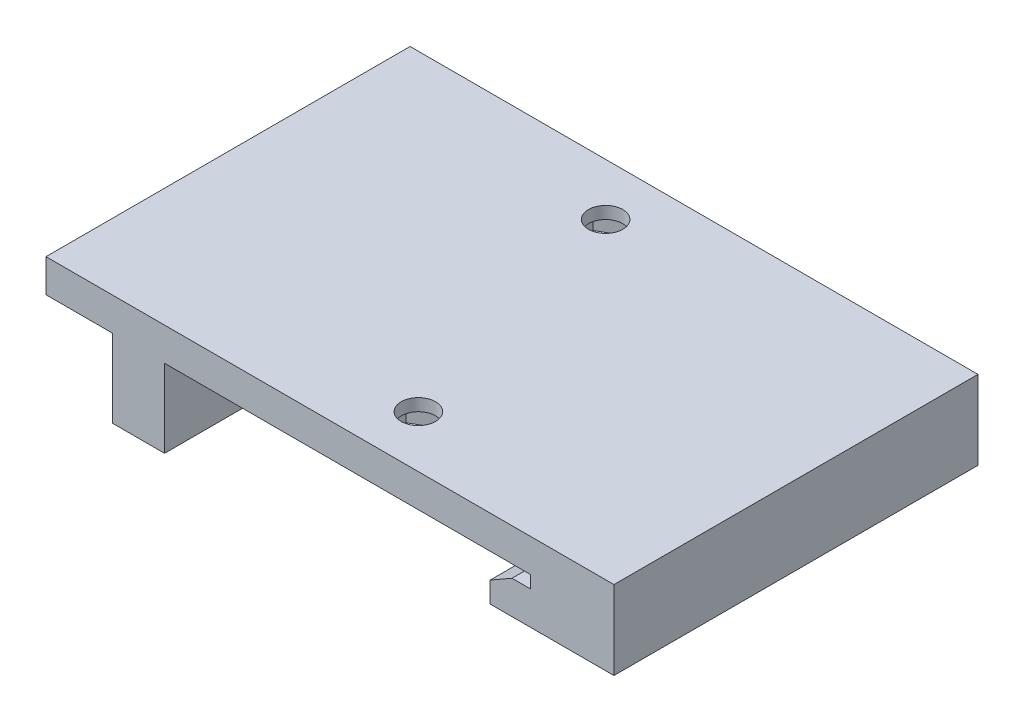
SolidWorks part; units mm, degrees
ref_plane "Front Plane" through (0, 0, 0) normal (0, 0, 1) x (1, 0, 0)
ref_plane "Top Plane" through (0, 0, 0) normal (0, 1, 0) x (1, 0, 0)
ref_plane "Right Plane" through (0, 0, 0) normal (1, 0, 0) x (0, 0, -1)
sketch "Sketch1" plane through (0, 0, 0) normal (0, 0, 1) x (1, 0, 0)
  line L0 (0, 0) -> (19.3, 0)
  line L1 (19.3, 0) -> (19.3, -1.2)
  line L2 (19.3, -1.2) -> (17.5, -1.2)
  line L3 (17.5, -1.2) -> (15.4, -2.4)
  line L4 (15.4, -2.4) -> (15.4, -4.4)
  line L5 (15.4, -4.4) -> (27.3, -4.4)
  line L8 (27.3, 3.175) -> (-27.3, 3.175)
  line L10 (-20.9, -7.5) -> (-15.9, -7.5)
  line L11 (-15.9, -7.5) -> (-15.9, 0)
  line L12 (-15.9, 0) -> (0, 0)
  line L16 (0, 0) -> (0, 6.355) construction
  line L20 (27.3, 3.175) -> (27.3, -4.4)
  line L21 (-27.3, 3.175) -> (-27.3, 0)
  line L22 (-27.3, 0) -> (-20.9, 0)
  line L23 (-20.9, 0) -> (-20.9, -7.5)
  dimension "D2" = 1.8
  dimension "D3" = 3.9
  dimension "D4" = 3.2
  dimension "D5" = 1.2
  dimension "D6" = 1.2
  dimension "D7" = 5
  dimension "D8" = 7.5
  dimension "D9" = 3.175
  dimension "D10" = 15.4
  dimension "D11" = 54.6
  dimension "D14" = 15.9
extrude "Boss-Extrude1" add sketch "Sketch1" along normal blind 35
sketch "Sketch2" plane through (-20.9, 0, 0) normal (-1, 0, 0) x (0, 0, 1)
  line L0 (17.5, 0) -> (17.5, -7.5) construction
  line L1 (35, 0) -> (0, 0) construction
  line L2 (35, -7.5) -> (0, -7.5) construction
  line L3 (0, 0) -> (17.5, 0) construction
  line L4 (8.75, 0) -> (8.75, -7.5) construction
  line L5 (17.5, 0) -> (35, 0) construction
  line L6 (26.25, 0) -> (26.25, -7.5) construction
  circle A0 centre (8.75, -3.75) radius 1.275
  circle A1 centre (26.25, -3.75) radius 1.275
  point P10 (17.5, -3.75)
  dimension "D1" = 2.55
extrude "Cut-Extrude1" cut sketch "Sketch2" against normal up to surface (5 mm away) up to face at (-15.9, -3.75, 17.5)
sketch "Sketch5" plane through (0, 0, 0) normal (0, -1, 0) x (1, 0, 0)
  line L0 (-15.9, 35) -> (19.3, 35) construction
  line L1 (6.35, 28.3546) -> (6.35, 31.6454)
  line L2 (6.35, 31.6454) -> (3.5, 33.2909)
  line L3 (3.5, 33.2909) -> (0.65, 31.6454)
  line L4 (0.65, 31.6454) -> (0.65, 28.3546)
  line L5 (0.65, 28.3546) -> (3.5, 26.7091)
  line L6 (3.5, 26.7091) -> (6.35, 28.3546)
  line L7 (-0.65, 6.6454) -> (-3.5, 8.2909)
  line L8 (-3.5, 8.2909) -> (-6.35, 6.6454)
  line L9 (-6.35, 6.6454) -> (-6.35, 3.3546)
  line L10 (-6.35, 3.3546) -> (-3.5, 1.7091)
  line L11 (-3.5, 1.7091) -> (-0.65, 3.3546)
  line L12 (-0.65, 3.3546) -> (-0.65, 6.6454)
  line L13 (-15.9, 0) -> (19.3, 0) construction
  circle A0 centre (3.5, 30) radius 2.85 construction
  circle A1 centre (-3.5, 5) radius 2.85 construction
  circle A2 centre (3.5, 30) radius 1.65
  circle A3 centre (-3.5, 5) radius 1.65
  dimension "D4" = 3.3
  dimension "D1" = 5.7
  dimension "D2" = 5
  dimension "D3" = 5
  dimension "D5" = 7
  dimension "D6" = 3.5
extrude "Cut-Extrude2" cut sketch "Sketch5" against normal blind 2
sketch "Sketch6" plane through (0, 0, 0) normal (0, -1, 0) x (1, 0, 0)
  circle A0 centre (3.5, 30) radius 1.65 construction
  circle A1 centre (3.5, 30) radius 1.65
  circle A3 centre (-3.5, 5) radius 1.65
  circle A4 centre (-3.5, 5) radius 1.65
  dimension "D1" = 0
extrude "Cut-Extrude3" cut sketch "Sketch6" against normal through all
